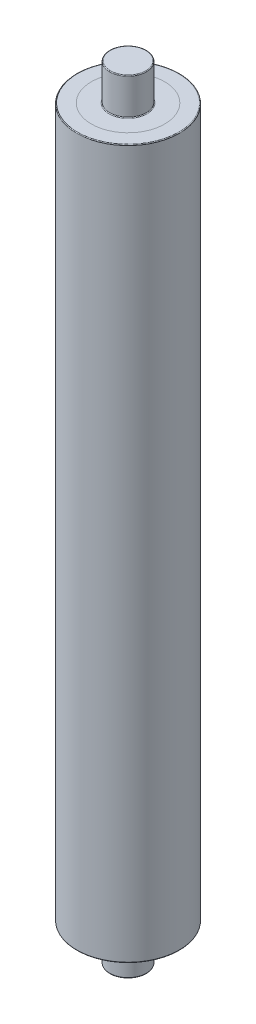
SolidWorks part; units mm, degrees
ref_plane "Ön Düzlem" through (0, 0, 0) normal (0, 0, 1) x (1, 0, 0)
ref_plane "Üst Düzlem" through (0, 0, 0) normal (0, 1, 0) x (1, 0, 0)
ref_plane "Sağ Düzlem" through (0, 0, 0) normal (1, 0, 0) x (0, 0, -1)
sketch "Sketch1" plane through (0, 0, 0) normal (0, 0, 1) x (1, 0, 0)
  line L0 (0, 0) -> (0, 320)
  line L1 (0, 320) -> (7.5, 320)
  line L2 (7.5, 320) -> (7.5, 305)
  line L3 (7.5, 305) -> (21, 305)
  line L4 (21, 305) -> (21, 15)
  line L5 (21, 15) -> (7.5, 15)
  line L6 (7.5, 15) -> (7.5, 0)
  line L7 (7.5, 0) -> (0, 0)
  dimension "D1" = 7.5
  dimension "D2" = 21
  dimension "D3" = 15
  dimension "D4" = 290
revolve "Revolve1" add sketch "Sketch1" angle 360 about L0
fillet "Fillet1" radius 0.3 6 edges at (0, 0, -7.5) (0, 15, -7.5) (0, 15, -21) (0, 320, -7.5) (0, 305, -21) (0, 305, -7.5)
sketch "Sketch2" plane through (0, 15, 0) normal (0, -1, 0) x (1, 0, 0)
  circle A0 centre (0, 0) radius 15 construction
  dimension "D1" = 30
sketch "Sketch3" plane through (0, 305, 0) normal (0, 1, 0) x (1, 0, 0)
  circle A2 centre (0, 0) radius 15
  circle A3 centre (0, 0) radius 15
  dimension "D1" = 0
surface "Surface-Extrude1" sketch "Sketch3"
split line "Split Line1"
ref_axis "Axis1" through (0, 302.1862, 0) along (0, -1, 0)
